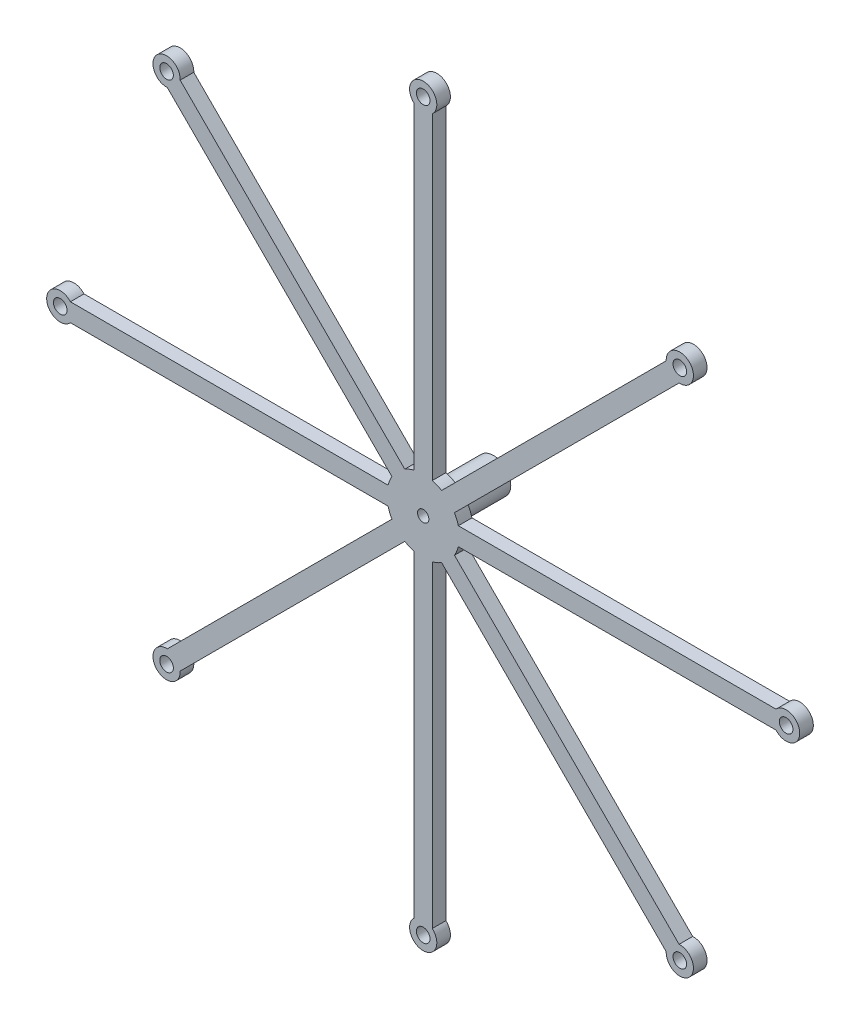
SolidWorks part; units mm, degrees
note: '?' marks a value the reader was unsure of.
ref_plane "前视基准面" through (0, 0, 0) normal (0, 0, 1) x (1, 0, 0)
ref_plane "上视基准面" through (0, 0, 0) normal (0, 1, 0) x (1, 0, 0)
ref_plane "右视基准面" through (0, 0, 0) normal (1, 0, 0) x (0, 0, -1)
other "Configuration Table"
ref_axis "基准轴1" through (0, 0, 0) along (0, 0, 1)?
sketch "草图1" plane through (0, 0, 0) normal (0, 0, 1) x (1, 0, 0)
  circle A0 centre (0, 0) radius 8
  dimension "D1" = 16
extrude "凸台-拉伸1" add sketch "草图1" along normal blind 3
sketch "草图2" plane through (0, 0, 3) normal (0, 0, 1) x (1, 0, 0)
  line L0 (0, 0) -> (80, 0) construction
  line L1 (77.7639, 2) -> (7.746, 2)
  line L2 (7.746, -2) -> (77.7639, -2)
  circle A0 centre (80, 0) radius 1.5
  circle A1 centre (80, 0) radius 3
  circle A2 centre (0, 0) radius 8 construction
  dimension "D2" = 6
  dimension "D3" = 3
  dimension "D1" = 4
  dimension "D4" = 80
extrude "凸台-拉伸-辐条" add sketch "草图2" against normal up to surface (3 mm away)
pattern_circular "阵列(圆周)3" count 8 over 360 about axis through (0, 0, 0) along (0, 0, 1) of "凸台-拉伸-辐条"
sketch "草图3" plane through (0, 0, 0) normal (0, 0, -1) x (-1, 0, 0)
  circle A0 centre (0, 0) radius 3.8
  dimension "D1" = 7.6
extrude "凸台-拉伸3" add sketch "草图3" along normal up to surface (12.5 mm away)
sketch "草图4" plane through (0, 0, -12.5) normal (0, 0, -1) x (-1, 0, 0)
  circle A0 centre (0, 0) radius 1.25
  dimension "D1" = 2.5
extrude "切除-拉伸1" cut sketch "草图4" against normal through all
